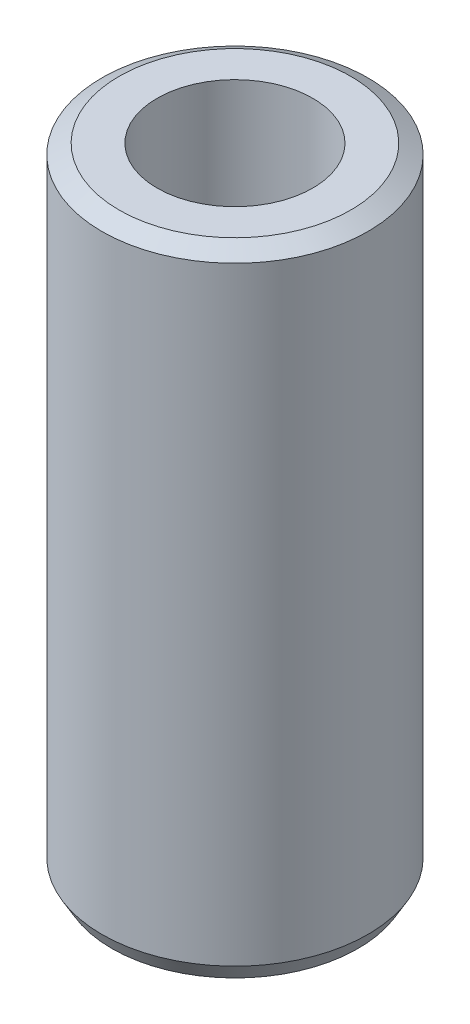
SolidWorks part; units mm, degrees
ref_plane "Front Plane" through (0, 0, 0) normal (0, 0, 1) x (1, 0, 0)
ref_plane "Top Plane" through (0, 0, 0) normal (0, 1, 0) x (1, 0, 0)
ref_plane "Right Plane" through (0, 0, 0) normal (1, 0, 0) x (0, 0, -1)
sketch "Sketch1" plane through (0, 0, 0) normal (0, 1, 0) x (1, 0, 0)
  circle A0 centre (0, 0) radius 20
  dimension "SHAFT_OD" = 40
extrude "Boss-Extrude1" add sketch "Sketch1" along normal blind 95.5706
sketch "Sketch2" plane through (0, 0, 0) normal (0, 1, 0) x (1, 0, 0)
  circle A0 centre (0, 0) radius 11.7001
  dimension "BORE_D" = 23.4002
extrude "Cut-Extrude1" cut sketch "Sketch2" along normal through all
chamfer "Chamfer1" distance 1.4942 angle 60 2 edges at (0, 95.5706, 20) (0, 0, 20) first distance on face at (0, 95.5706, 20) first distance on face at (0, 0, 11.7001)
